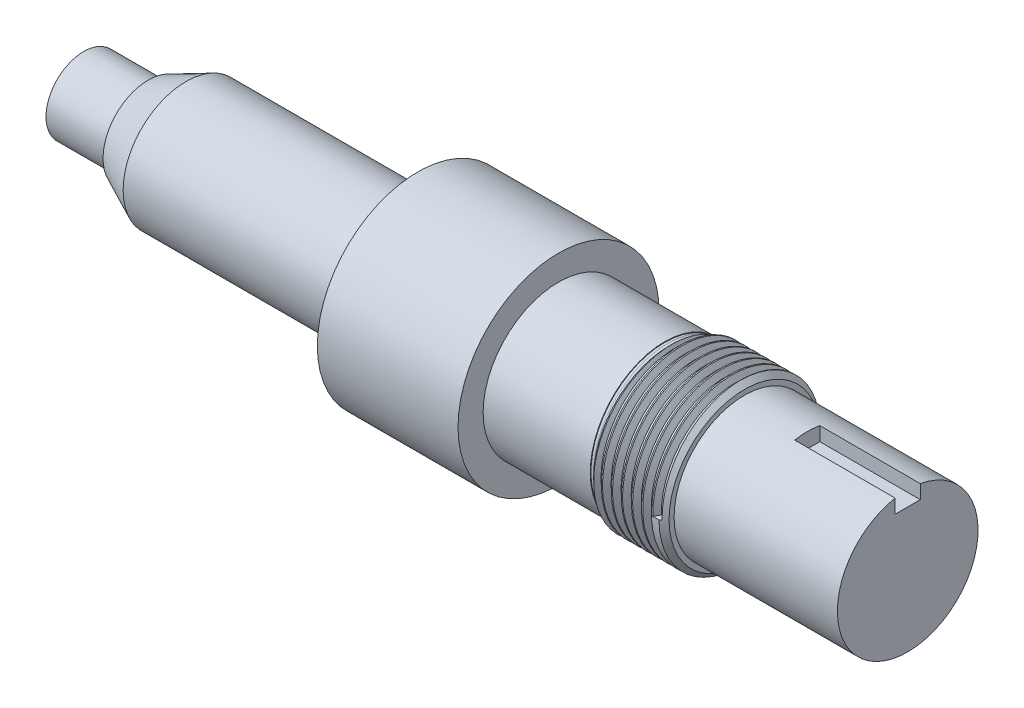
SolidWorks part; units mm, degrees
ref_plane "Front" through (0, 0, 0) normal (0, 0, 1) x (1, 0, 0)
ref_plane "Top" through (0, 0, 0) normal (0, 1, 0) x (1, 0, 0)
ref_plane "Right" through (0, 0, 0) normal (1, 0, 0) x (0, 0, -1)
sketch "Çizim1" plane through (0, 0, 0) normal (0, 0, 1) x (1, 0, 0)
  line L0 (0, 0) -> (0, 28)
  line L1 (0, 28) -> (-45, 28)
  line L2 (-45, 28) -> (-45, 32)
  line L3 (-45, 32) -> (-75, 32)
  line L4 (-75, 32) -> (-75, 30)
  line L7 (-308, 0) -> (0, 0)
  line L8 (-75, 30) -> (-119, 30)
  line L9 (-119, 30) -> (-119, 40)
  line L10 (-119, 40) -> (-175, 40)
  line L11 (-175, 40) -> (-175, 25)
  line L12 (-175, 25) -> (-267.3, 25)
  line L14 (-282.3, 18) -> (-282.3, 15)
  line L15 (-282.3, 15) -> (-308, 15)
  line L16 (-308, 15) -> (-308, 0)
  line L17 (-267.3, 25) -> (-282.3, 18)
  dimension "D1" = 32
  dimension "D2" = 28
  dimension "D3" = 30
  dimension "D4" = 30
  dimension "D5" = 45
  dimension "D6" = 44
  dimension "D7" = 40
  dimension "D8" = 25
  dimension "D9" = 56
  dimension "D10" = 163.3
  dimension "D11" = 15
  dimension "D12" = 308
  dimension "D13" = 15
  dimension "D14" = 18
revolve "Döndür1" add sketch "Çizim1" angle 360 about L7
chamfer "Pah1" distance 2 angle 45 2 edges at (-75, 0, 32) (-45, 0, 32)
thread "Diş1" pitch 4 method cut profile "Diş Profili1" start angle 0, offset 1, length 30, pitch 4, diameter 64
ref_plane "Düzlem1" through (-46, 0, 32) normal (0, -1, 0) x (0, 0, 1)
sketch "Diş Profili1" plane through (-46, 0, 32) normal (0, -1, 0) x (0, 0, 1)
  line L0 (0, 0) -> (0, 4) construction
  line L11 (0, 0) -> (0, 3.5)
  line L12 (0, 3.5) -> (-2.1651, 2.25)
  line L13 (-2.1651, 2.25) -> (-2.1651, 1.25)
  line L15 (-2.1651, 1.25) -> (0, 0)
  line L17 (-2.1651, 1.75) -> (0, 1.75) construction
  point P2 (0, 0)
  dimension "Pitch" = 4
  dimension "Profile_Angle" = 60
  dimension "Profile_Land" = 1
  dimension "Profile_Height" = 2.1651
sketch "Çizim6" plane through (0, 0, 0) normal (1, 0, 0) x (0, 0, -1)
  line L1 (-5, 35.9755) -> (5, 35.9755)
  line L2 (-5, 35.9755) -> (-5, 22)
  line L3 (-5, 22) -> (5, 22)
  line L4 (5, 35.9755) -> (5, 22)
  dimension "D1" = 10
  dimension "D2" = 5
  dimension "D3" = 22
extrude "Kes-Ekstrüzyon1" cut sketch "Çizim6" against normal blind 20
sketch "Çizim7" plane through (0, 0, 0) normal (1, 0, 0) x (0, 0, -1)
  line L3 (5, 22) -> (-5, 22)
  line L4 (-5, 22) -> (-5, 27.55)
  line L5 (5, 27.55) -> (5, 22)
  line L6 (5, 22) -> (-5, 22)
  line L7 (-5, 22) -> (-5, 27.55)
  line L8 (5, 27.55) -> (5, 22)
  arc A1 (-5, 27.55) -> (5, 27.55) centre (0, 0) ccw
  arc A2 (-5, 27.55) -> (5, 27.55) centre (0, 0) ccw
  dimension "D1" = 0
extrude "Yükseklik-Ekstrüzyon1" add sketch "Çizim7" along normal blind 20
